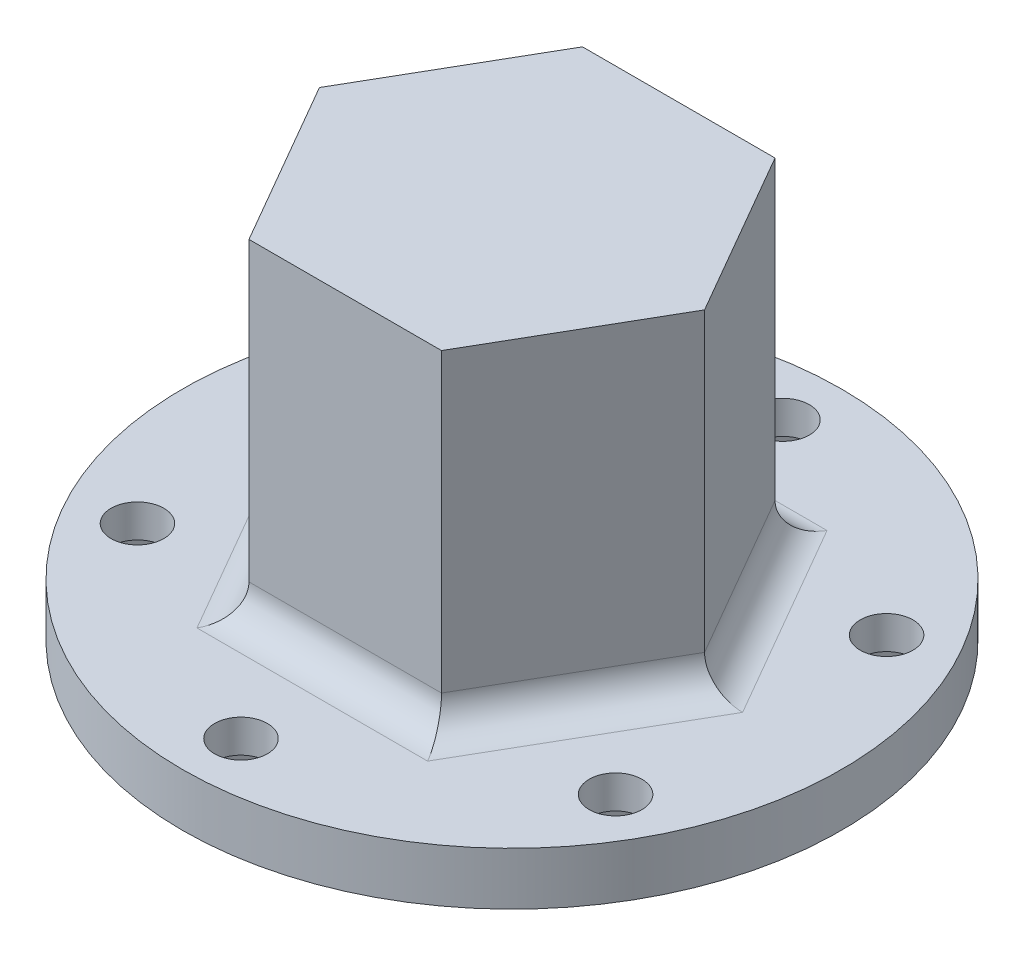
SolidWorks part; units mm, degrees
ref_plane "Front Plane" through (0, 0, 0) normal (0, 0, 1) x (1, 0, 0)
ref_plane "Top Plane" through (0, 0, 0) normal (0, 1, 0) x (1, 0, 0)
ref_plane "Right Plane" through (0, 0, 0) normal (1, 0, 0) x (0, 0, -1)
sketch "Sketch1" plane through (0, 0, 0) normal (0, 1, 0) x (1, 0, 0)
  line L0 (11.547, -20) -> (23.094, 0)
  line L1 (23.094, 0) -> (11.547, 20)
  line L2 (11.547, 20) -> (-11.547, 20)
  line L3 (-11.547, 20) -> (-23.094, 0)
  line L4 (-23.094, 0) -> (-11.547, -20)
  line L5 (-11.547, -20) -> (11.547, -20)
  line L6 (11.7202, -20.3) -> (23.4404, 0)
  line L7 (23.4404, 0) -> (11.7202, 20.3)
  line L8 (11.7202, 20.3) -> (-11.7202, 20.3)
  line L9 (-11.7202, 20.3) -> (-23.4404, 0)
  line L10 (-23.4404, 0) -> (-11.7202, -20.3)
  line L11 (-11.7202, -20.3) -> (11.7202, -20.3)
  line L12 (-14.607, -25.3) -> (14.607, -25.3)
  line L13 (14.607, -25.3) -> (29.2139, 0)
  line L14 (29.2139, 0) -> (14.607, 25.3)
  line L15 (14.607, 25.3) -> (-14.607, 25.3)
  line L16 (-14.607, 25.3) -> (-29.2139, 0)
  line L17 (-29.2139, 0) -> (-14.607, -25.3)
  dimension "D1" = 0.3
  dimension "D2" = 5
extrude "Boss-Extrude1" add sketch "Sketch1" along normal blind 50 contours L16 L17 L12 L13 L14 L15 L11 L10 L9 L8 L7 L6 region at (-21.2411, 0, 12.2635)
sketch "Sketch2" plane through (0, 50, 0) normal (0, 1, 0) x (1, 0, 0)
  line L6 (-14.607, 25.3) -> (-29.2139, 0)
  line L7 (-29.2139, 0) -> (-14.607, -25.3)
  line L8 (-14.607, -25.3) -> (14.607, -25.3)
  line L9 (14.607, -25.3) -> (29.2139, 0)
  line L10 (29.2139, 0) -> (14.607, 25.3)
  line L11 (14.607, 25.3) -> (-14.607, 25.3)
  line L12 (-14.607, 25.3) -> (-29.2139, 0)
  line L13 (-29.2139, 0) -> (-14.607, -25.3)
  line L14 (-14.607, -25.3) -> (14.607, -25.3)
  line L15 (14.607, -25.3) -> (29.2139, 0)
  line L16 (29.2139, 0) -> (14.607, 25.3)
  line L17 (14.607, 25.3) -> (-14.607, 25.3)
  dimension "D1" = 0
extrude "Boss-Extrude2" add sketch "Sketch2" along normal blind 5
sketch "Sketch3" plane through (0, 0, 0) normal (0, -1, 0) x (1, 0, 0)
  line L0 (11.7202, -20.3) -> (-11.7202, -20.3) construction
  line L1 (-11.7202, -20.3) -> (-23.4404, 0) construction
  line L2 (-23.4404, 0) -> (-11.7202, 20.3) construction
  line L3 (-11.7202, 20.3) -> (11.7202, 20.3) construction
  line L4 (11.7202, 20.3) -> (23.4404, 0) construction
  line L5 (23.4404, 0) -> (11.7202, -20.3) construction
  line L6 (29.2139, 0) -> (14.607, -25.3) construction
  line L7 (14.607, -25.3) -> (-14.607, -25.3) construction
  line L8 (-14.607, -25.3) -> (-29.2139, 0) construction
  line L9 (-29.2139, 0) -> (-14.607, 25.3) construction
  line L10 (-14.607, 25.3) -> (14.607, 25.3) construction
  line L11 (14.607, 25.3) -> (29.2139, 0) construction
  line L12 (11.7202, -20.3) -> (-11.7202, -20.3)
  line L13 (-11.7202, -20.3) -> (-23.4404, 0)
  line L14 (-23.4404, 0) -> (-11.7202, 20.3)
  line L15 (-11.7202, 20.3) -> (11.7202, 20.3)
  line L16 (11.7202, 20.3) -> (23.4404, 0)
  line L17 (23.4404, 0) -> (11.7202, -20.3)
  line L18 (29.2139, 0) -> (14.607, -25.3)
  line L19 (14.607, -25.3) -> (-14.607, -25.3)
  line L20 (-14.607, -25.3) -> (-29.2139, 0)
  line L21 (-29.2139, 0) -> (-14.607, 25.3)
  line L22 (-14.607, 25.3) -> (14.607, 25.3)
  line L23 (14.607, 25.3) -> (29.2139, 0)
  circle A1 centre (0, 0) radius 50
  line M2 (-11.7202, 20.3) -> (11.7202, 20.3)
  line M3 (11.7202, 20.3) -> (23.4404, 0)
  line M4 (23.4404, 0) -> (11.7202, -20.3)
  line M5 (11.7202, -20.3) -> (-11.7202, -20.3)
  line M6 (-11.7202, -20.3) -> (-23.4404, 0)
  line M7 (-23.4404, 0) -> (-11.7202, 20.3)
  line M8 (-29.2139, 0) -> (-14.607, -25.3)
  line M9 (-14.607, -25.3) -> (14.607, -25.3)
  line M10 (14.607, -25.3) -> (29.2139, 0)
  line M11 (29.2139, 0) -> (14.607, 25.3)
  line M12 (14.607, 25.3) -> (-14.607, 25.3)
  line M13 (-14.607, 25.3) -> (-29.2139, 0)
extrude "Boss-Extrude3" add sketch "Sketch3" against normal blind 5 contours A1 M8 M13 M12 M11 M10 M9 | M13 M8 M9 M10 M11 M12 M7 M2 M3 M4 M5 M6 region at (21.2411, 0, -12.2635) region at (-48.5858, 0, 0)
fillet "Fillet1" radius 5 6 edges at (0, 5, 25.3) (21.9104, 5, 12.65) (21.9104, 5, -12.65) (0, 5, -25.3) (-21.9104, 5, 12.65) (-21.9104, 5, -12.65)
sketch "Sketch5" plane through (0, 0, 0) normal (0, -1, 0) x (1, 0, 0)
  line L24 (-3.4841, 34.7982) -> (-7.3524, 41.4982)
  line L25 (4.2524, 34.7982) -> (-3.4841, 34.7982)
  line L26 (8.1206, 41.4982) -> (4.2524, 34.7982)
  line L27 (4.2524, 48.1982) -> (8.1206, 41.4982)
  line L28 (-3.4841, 48.1982) -> (4.2524, 48.1982)
  line L29 (-7.3524, 41.4982) -> (-3.4841, 48.1982)
  line L42 (28.3941, 20.4164) -> (32.2623, 27.1164)
  line L43 (32.2623, 13.7164) -> (28.3941, 20.4164)
  line L44 (39.9988, 13.7164) -> (32.2623, 13.7164)
  line L45 (43.8671, 20.4164) -> (39.9988, 13.7164)
  line L46 (39.9988, 27.1164) -> (43.8671, 20.4164)
  line L47 (32.2623, 27.1164) -> (39.9988, 27.1164)
  line L60 (31.8782, -14.3818) -> (39.6147, -14.3818)
  line L61 (28.01, -21.0818) -> (31.8782, -14.3818)
  line L62 (31.8782, -27.7818) -> (28.01, -21.0818)
  line L63 (39.6147, -27.7818) -> (31.8782, -27.7818)
  line L64 (43.4829, -21.0818) -> (39.6147, -27.7818)
  line L65 (39.6147, -14.3818) -> (43.4829, -21.0818)
  line L66 (3.4841, -34.7982) -> (7.3524, -41.4982)
  line L67 (-4.2524, -34.7982) -> (3.4841, -34.7982)
  line L68 (-8.1206, -41.4982) -> (-4.2524, -34.7982)
  line L69 (-4.2524, -48.1982) -> (-8.1206, -41.4982)
  line L70 (3.4841, -48.1982) -> (-4.2524, -48.1982)
  line L71 (7.3524, -41.4982) -> (3.4841, -48.1982)
  line L72 (-28.3941, -20.4164) -> (-32.2623, -27.1164)
  line L73 (-32.2623, -13.7164) -> (-28.3941, -20.4164)
  line L74 (-39.9988, -13.7164) -> (-32.2623, -13.7164)
  line L75 (-43.8671, -20.4164) -> (-39.9988, -13.7164)
  line L76 (-39.9988, -27.1164) -> (-43.8671, -20.4164)
  line L77 (-32.2623, -27.1164) -> (-39.9988, -27.1164)
  line L78 (-31.8782, 14.3818) -> (-39.6147, 14.3818)
  line L79 (-28.01, 21.0818) -> (-31.8782, 14.3818)
  line L80 (-31.8782, 27.7818) -> (-28.01, 21.0818)
  line L81 (-39.6147, 27.7818) -> (-31.8782, 27.7818)
  line L82 (-43.4829, 21.0818) -> (-39.6147, 27.7818)
  line L83 (-39.6147, 14.3818) -> (-43.4829, 21.0818)
  circle A1 centre (0, 0) radius 50
  circle A2 centre (0, 0) radius 50
  circle A6 centre (0.3841, 41.4982) radius 4
  circle A9 centre (36.1306, 20.4164) radius 4
  circle A10 centre (35.7464, -21.0818) radius 4
  circle A11 centre (-0.3841, -41.4982) radius 4
  circle A12 centre (-36.1306, -20.4164) radius 4
  circle A13 centre (-35.7464, 21.0818) radius 4
  point P53 (0, 0)
  line M28 (-11.7202, 20.3) -> (11.7202, 20.3)
  line M29 (11.7202, 20.3) -> (23.4404, 0)
  line M30 (23.4404, 0) -> (11.7202, -20.3)
  line M31 (11.7202, -20.3) -> (-11.7202, -20.3)
  line M32 (-11.7202, -20.3) -> (-23.4404, 0)
  line M33 (-23.4404, 0) -> (-11.7202, 20.3)
  circle M34 centre (0, 0) radius 50
  dimension "D4" = 41.5
  dimension "D1" = 0
  dimension "D2" = 6
extrude "Boss-Extrude4" add sketch "Sketch5" along normal blind 3 contours L62 L68 L24 L29 L28 L27 L26 L25 L74 L80 M34 M33 M28 M29 M30 M31 M32 region at (-48.5858, 0, 0)
extrude "Cut-Extrude1" cut sketch "Sketch5<3>" against normal blind 10 contours A6 | A13 | A10 | A11 | A12 | A9 region at (0.3841, 0, 41.4982)
sketch "Sketch5<3>" plane through (0, 0, 0) normal (0, -1, 0) x (1, 0, 0) same geometry as "Sketch5"
sketch "Sketch6" plane through (0, 55, 0) normal (0, 1, 0) x (1, 0, 0)
  line L6 (14.607, 25.3) -> (-14.607, 25.3)
  line L7 (-14.607, 25.3) -> (-29.2139, 0)
  line L8 (-29.2139, 0) -> (-14.607, -25.3)
  line L9 (-14.607, -25.3) -> (14.607, -25.3)
  line L10 (14.607, -25.3) -> (29.2139, 0)
  line L11 (29.2139, 0) -> (14.607, 25.3)
  line L12 (14.607, 25.3) -> (-14.607, 25.3)
  line L13 (-14.607, 25.3) -> (-29.2139, 0)
  line L14 (-29.2139, 0) -> (-14.607, -25.3)
  line L15 (-14.607, -25.3) -> (14.607, -25.3)
  line L16 (14.607, -25.3) -> (29.2139, 0)
  line L17 (29.2139, 0) -> (14.607, 25.3)
  dimension "D1" = 0
